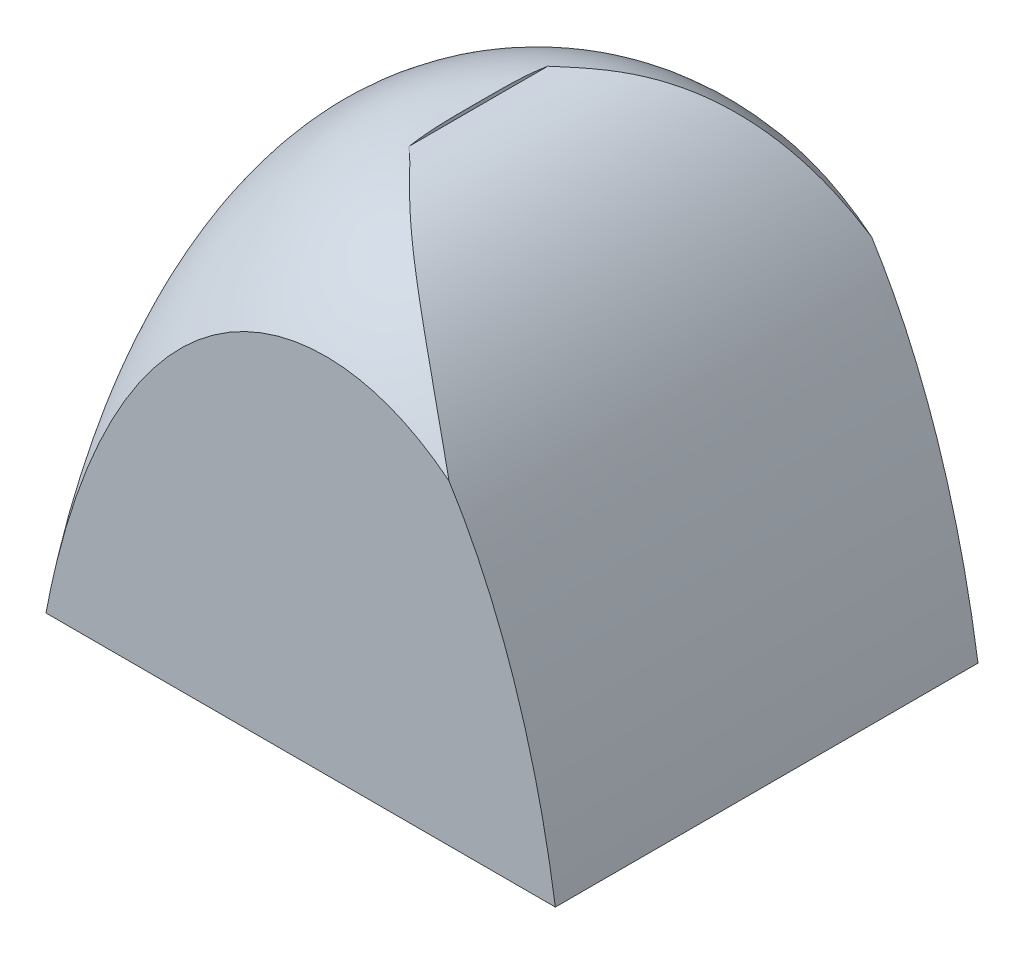
SolidWorks part; units mm, degrees
ref_plane "Front Plane" through (0, 0, 0) normal (0, 0, 1) x (1, 0, 0)
ref_plane "Top Plane" through (0, 0, 0) normal (0, 1, 0) x (1, 0, 0)
ref_plane "Right Plane" through (0, 0, 0) normal (1, 0, 0) x (0, 0, -1)
sketch "Sketch1" plane through (0, 0, 0) normal (0, 0, 1) x (1, 0, 0)
  line L0 (0, 0) -> (91.3948, 0) construction
  line L1 (0, -274.9226) -> (0, 50480.6925) construction
  ellipse E0 centre (0, 0) end of major axis (0, 712.2672) minor radius 343.2806
extrude "Boss-Extrude1" add sketch "Sketch1" along normal blind 237.5 and the other way blind 237.5
sketch "Sketch7" plane through (0, 0, 237.5) normal (0, 0, 1) x (1, 0, 0)
  line L1 (-553.6267, 209.5972) -> (494.8512, 209.5972)
  line L2 (-553.6267, 209.5972) -> (-553.6267, -734.6018)
  line L3 (-553.6267, -734.6018) -> (494.8512, -734.6018)
  line L4 (494.8512, 209.5972) -> (494.8512, -734.6018)
  line L5 (-553.6267, 209.5972) -> (494.8512, -734.6018) construction
  line L6 (-553.6267, -734.6018) -> (494.8512, 209.5972) construction
  ellipse E0 centre (0, 0) end of major axis (0, 712.2672) minor radius 343.2806 construction
  point P0 (-29.3877, -262.5023)
  point P6 (0, 712.2672)
  dimension "D1" = 502.67
extrude "Cut-Extrude2" cut sketch "Sketch7" against normal through all contours L1 L4 L3 L2
sketch "Sketch8" plane through (0, 0, 237.5) normal (0, 0, 1) x (1, 0, 0)
  line L0 (0, 708.2672) -> (0, 868.4904)
  line L1 (0, 868.4904) -> (516.5903, 876.6533)
  line L2 (516.5903, 876.6533) -> (527.14, 209.01)
  line L3 (527.14, 209.01) -> (324.1245, 209.01)
  spline S0 degree 3 poles (-1652.136, 479.9602) (78.1137, -1665.8296) (470.6123, -387.7521) (296.0424, 347.569) (286.7361, 379.9845) (265.778, 441.3213) (254.1264, 470.2419) (235.1198, 510.4485) (228.5299, 523.3223) (214.8854, 547.9312) (207.8308, 559.6662) (193.3046, 581.9226) (185.833, 592.444) (170.5237, 612.2066) (162.686, 621.4477) (146.6988, 638.5926) (138.5493, 646.4963) (121.9946, 660.9191) (113.5895, 667.4382) (96.5811, 679.0559) (87.9778, 684.1545) (70.6291, 692.907) (61.8838, 696.5609) (35.5132, 705.3356) (17.7555, 708.2672) (-17.7555, 708.2672) (-35.5132, 705.3356) (-61.8838, 696.5609) (-70.6291, 692.907) (-87.9778, 684.1545) (-96.5811, 679.0559) (-113.5895, 667.4382) (-121.9946, 660.9191) (-138.5493, 646.4963) (-146.6988, 638.5926) (-162.686, 621.4477) (-170.5237, 612.2066) (-185.833, 592.444) (-193.3046, 581.9226) (-207.8308, 559.6662) (-214.8854, 547.9312) (-228.5299, 523.3223) (-235.1198, 510.4485) (-254.1264, 470.2419) (-265.778, 441.3213) (-286.7361, 379.9845) (-296.0424, 347.569) (-470.6113, -387.748) (-78.1182, -1665.8147) (1652.1058, 479.9227) knots -1.236688 -1.236688 -1.236688 -1.236688 0.0625 0.0625 0.125 0.125 0.1875 0.1875 0.21875 0.21875 0.25 0.25 0.28125 0.28125 0.3125 0.3125 0.34375 0.34375 0.375 0.375 0.40625 0.40625 0.4375 0.4375 0.5 0.5 0.5625 0.5625 0.59375 0.59375 0.625 0.625 0.65625 0.65625 0.6875 0.6875 0.71875 0.71875 0.75 0.75 0.78125 0.78125 0.8125 0.8125 0.875 0.875 0.9375 0.9375 2.23668 2.23668 2.23668 2.23668 only from (324.1245, 209.01) to (-324.1245, 209.01)
  spline S1 degree 3 poles (324.1245, 209.01) (318.7863, 244.9835) (312.0675, 280.0681) (296.0424, 347.569) (286.7361, 379.9845) (265.778, 441.3213) (254.1264, 470.2419) (235.1198, 510.4485) (228.5299, 523.3223) (214.8854, 547.9312) (207.8308, 559.6662) (193.3046, 581.9226) (185.833, 592.444) (170.5237, 612.2066) (162.686, 621.4477) (146.6988, 638.5926) (138.5493, 646.4963) (121.9946, 660.9191) (113.5895, 667.4382) (96.5811, 679.0559) (87.9778, 684.1545) (70.6291, 692.907) (61.8838, 696.5609) (35.5132, 705.3356) (17.7555, 708.2672) (0, 708.2672) knots 0 0 0 0 0.0625 0.0625 0.125 0.125 0.1875 0.1875 0.21875 0.21875 0.25 0.25 0.28125 0.28125 0.3125 0.3125 0.34375 0.34375 0.375 0.375 0.40625 0.40625 0.4375 0.4375 0.5 0.5 0.5 0.5
  dimension "D1" = 4
extrude "Cut-Extrude3" cut sketch "Sketch8" against normal blind 475
sketch "Sketch11" plane through (0, 0, 0) normal (0, 0, 1) x (1, 0, 0)
  line L0 (-343.2806, 0) -> (-743.2267, 0)
  line L1 (-200000, 0) -> (200091.3948, 0) construction
  line L2 (-743.2267, 0) -> (-743.2267, 860.3411)
  line L3 (-743.2267, 860.3411) -> (0, 860.3411)
  line L4 (0, -200274.9226) -> (0, 250480.6925) construction
  line L5 (0, 860.3411) -> (0, 712.2672)
  line L6 (65.7962, 0) -> (65.7962, 545.5092) construction
  ellipse E0 centre (0, 0) end of major axis (0, 712.2672) minor radius 343.2806 construction
  ellipse E1 centre (0, 0) end of major axis (0, 712.2672) minor radius 343.2806 (0, 712.2672) -> (-343.2806, 0) ccw
  dimension "D1" = 409.0768
revolve "Cut-Revolve2" cut sketch "Sketch11" angle 360 about L6
